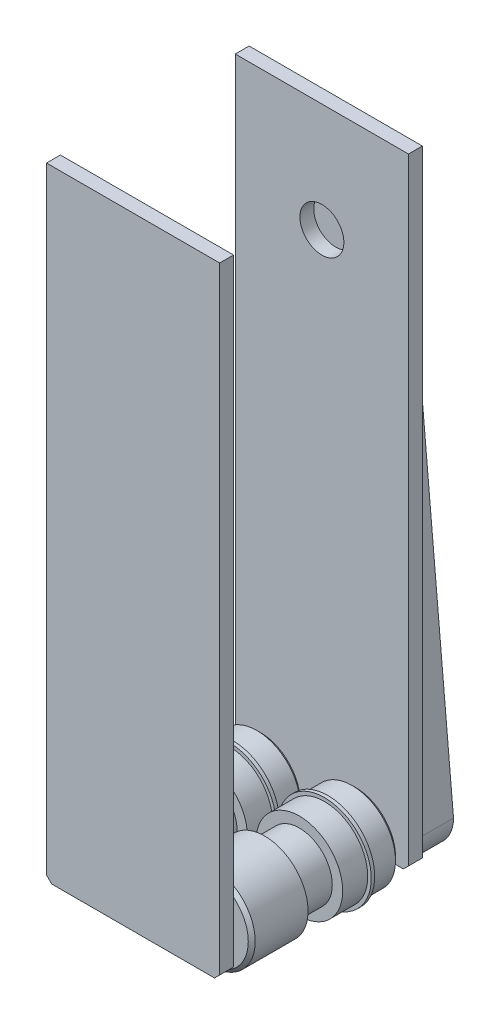
SolidWorks part; units mm, degrees
ref_plane "前视基准面" through (0, 0, 0) normal (0, 0, 1) x (1, 0, 0)
ref_plane "上视基准面" through (0, 0, 0) normal (0, 1, 0) x (1, 0, 0)
ref_plane "右视基准面" through (0, 0, 0) normal (1, 0, 0) x (0, 0, -1)
sketch "草图1" plane through (0, 0, 0) normal (0, 0, 1) x (1, 0, 0)
  line L0 (0, 39.4413) -> (0, -42.5415) construction
  line L1 (-27.5, 0) -> (27.5, 0) construction
  circle A0 centre (-27.5, 0) radius 25
  circle A1 centre (27.5, 0) radius 25
  dimension "D2" = 50
  dimension "D1" = 55
extrude "凸台-拉伸1" add sketch "草图1" along normal mid plane 85
sketch "草图2" plane through (0, 0, 0) normal (0, 0, 1) x (1, 0, 0)
  circle A0 centre (-27.5, 0) radius 25
  circle A1 centre (27.5, 0) radius 25
  circle A2 centre (-27.5, 0) radius 19
  circle A3 centre (27.5, 0) radius 19
  circle A4 centre (27.5, 0) radius 25 construction
  circle A5 centre (-27.5, 0) radius 25 construction
  dimension "D1" = 6
  dimension "D2" = 6
extrude "切除-拉伸1" cut sketch "草图2" against normal mid plane 20
chamfer "倒角1" distance 2 angle 45 2 edges at (52.5, 0, 42.5) (52.5, 0, -42.5)
sketch "草图3" plane through (0, 0, -42.5) normal (0, 0, -1) x (-1, 0, 0)
  circle A0 centre (-27.5, 0) radius 5
  circle A1 centre (27.5, 0) radius 5
  circle A2 centre (27.5, 0) radius 25 construction
  dimension "D1" = 10
  dimension "D2" = 10
extrude "凸台-拉伸2" add sketch "草图3" along normal blind 8
mirror "镜向1" about plane through (0, 0, 0) normal (0, 0, 1) of "凸台-拉伸2"
sketch "草图4" plane through (0, 0, -50.5) normal (0, 0, -1) x (-1, 0, 0)
  line L0 (0, -25.1952) -> (0, -400) construction
  line L1 (-50, -12) -> (50, -12)
  line L2 (-50, -12) -> (-50, 347)
  line L3 (-50, 347) -> (50, 347)
  line L4 (50, -12) -> (50, 347)
  circle A2 centre (-27.5, 0) radius 23 construction
  dimension "D1" = 12
  dimension "D2" = 347
  dimension "D3" = 100
extrude "凸台-拉伸3" add sketch "草图4" along normal blind 8
mirror "镜向2" about plane through (0, 0, 0) normal (0, 0, 1) of "凸台-拉伸3"
chamfer "倒角2" distance 3 angle 45 4 edges at (50, -12, 54.5) (-50, -12, 54.5) (50, -12, -54.5) (-50, -12, -54.5)
sketch "草图5" plane through (0, 0, -58.5) normal (0, 0, -1) x (-1, 0, 0)
  circle A0 centre (27.5, 0) radius 19
  circle A1 centre (-27.5, 0) radius 19
  circle A2 centre (27.5, 0) radius 25 construction
  circle A3 centre (-27.5, 0) radius 25 construction
  dimension "D1" = 38
  dimension "D2" = 38
extrude "凸台-拉伸4" add sketch "草图5" along normal blind 22
sketch "草图7" plane through (0, 0, -50.5) normal (0, 0, 1) x (1, 0, 0)
  circle A0 centre (0, 284.1285) radius 12.6912
extrude "切除-拉伸2" cut sketch "草图7" against normal blind 10
sketch "草图8" plane through (0, 0, -58.5) normal (0, 0, -1) x (-1, 0, 0)
  circle A0 centre (0, 284.1285) radius 19
  dimension "D1" = 38
extrude "凸台-拉伸5" add sketch "草图8" along normal blind 20
sketch "草图9" plane through (0, 0, -58.5) normal (0, 0, -1) x (-1, 0, 0)
  line L0 (-47.9926, 0) -> (-22.254, 286.1304)
  line L1 (22.2562, 286.1053) -> (47.667, 0)
  line L2 (-27.5, -20.4926) -> (27.5, -20.167)
  line L3 (18.834, 289.5344) -> (44.2448, 3.4291)
  line L4 (-45.0723, 3.2007) -> (-19.5149, 285.8928)
  line L5 (-27.5, -17.7891) -> (27.5, -16.9825)
  arc A0 (22.2562, 286.1053) -> (-22.254, 286.1304) centre (0, 284.1285) ccw
  arc A1 (27.5, -20.167) -> (47.3513, 3.5543) centre (27.5, 0) ccw
  arc A2 (-47.6636, 3.6572) -> (-27.2574, -20.4911) centre (-27.5, 0) ccw
  arc A3 (18.834, 289.5344) -> (-19.5149, 285.8928) centre (0, 284.1285) ccw
  arc A6 (-27.5, -17.7891) -> (-26.9784, -17.7814) centre (-27.5, 0) ccw
  arc A7 (-45.0723, 3.2007) -> (-27.5, -17.7891) centre (-27.5, 0.0614) ccw
  arc A8 (44.2448, 3.4291) -> (27.5, -16.9825) centre (27.0019, 0.5003) cw
  line M4 (42.2309, -12) -> (47, -12)
  line M10 (-47, -12) -> (-42.2309, -12)
extrude "凸台-拉伸6" add sketch "草图9" along normal blind 20 contours A8 L5 A6 A7 A2 L2 A1 M4 M10 | L3 A8 A1 L1 A0 L0 A2 A7 L4 A3 M4 M10 region at (47.4888, 1.7981, -58.5)
chamfer "倒角3" distance 2 angle 45 3 edges at (-19, 284.1285, -78.5) (8.5, 0, -80.5) (-46.5, 0, -80.5)
chamfer "倒角4" distance 2 angle 45 2 edges at (-2.5, 0, -42.5) (-2.5, 0, 42.5)
ref_plane "基准面1" through (0, 0, -24.5) normal (0, 0, -1) x (-1, 0, 0)
sketch "草图11" plane through (0, 0, -24.5) normal (0, 0, -1) x (-1, 0, 0)
  circle A0 centre (27.5, 0) radius 27
  circle A1 centre (-27.5, 0) radius 27
  dimension "D1" = 54
  dimension "D2" = 54
extrude "凸台-拉伸8" add sketch "草图11" along normal blind 2
